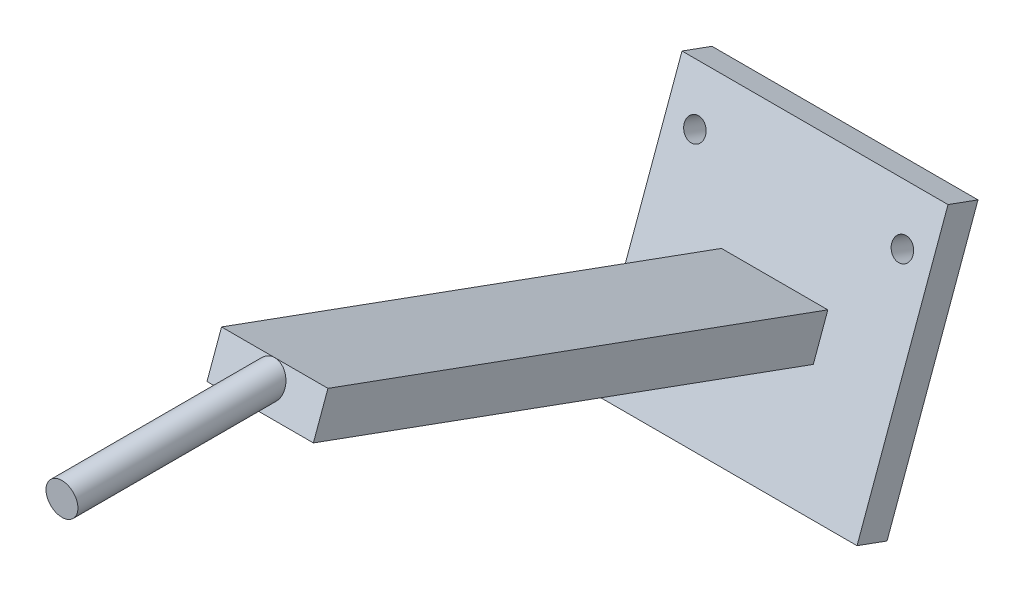
SolidWorks part; units mm, degrees
material "2024 合金"
ref_plane "前视基准面" through (0, 0, 0) normal (0, 0, 1) x (1, 0, 0)
ref_plane "上视基准面" through (0, 0, 0) normal (0, 1, 0) x (1, 0, 0)
ref_plane "右视基准面" through (0, 0, 0) normal (1, 0, 0) x (0, 0, -1)
sketch "草图1" plane through (0, 0, 0) normal (0, 0, 1) x (1, 0, 0)
  circle A0 centre (0, 0) radius 1.5
  dimension "D1" = 3
extrude "凸台-拉伸1" add sketch "草图1" along normal blind 20
sketch "草图2" plane through (0, 0, 0) normal (1, 0, 0) x (0, 0, -1)
  line L0 (0, 1.5) -> (-1.3681, -2.2588)
  line L1 (-1.3681, -2.2588) -> (45.6166, -19.3598)
  line L2 (45.6166, -19.3598) -> (46.9846, -15.601)
  line L3 (46.9846, -15.601) -> (0, 1.5)
  line L4 (0, 0) -> (0, 1.5) construction
  dimension "D1" = 20
  dimension "D2" = 4
  dimension "D3" = 50
extrude "凸台-拉伸2" add sketch "草图2" along normal blind 5 and the other way blind 5
sketch "草图3" plane through (0, -16.9255, -46.5025) normal (0, -0.342, -0.9397) x (-1, 0, 0)
  line L1 (-12.5, 12.5) -> (12.5, 12.5)
  line L2 (-12.5, 12.5) -> (-12.5, -12.5)
  line L3 (-12.5, -12.5) -> (12.5, -12.5)
  line L4 (12.5, 12.5) -> (12.5, -12.5)
  line L5 (-12.5, 12.5) -> (12.5, -12.5) construction
  line L6 (-12.5, -12.5) -> (12.5, 12.5) construction
  point P0 (0, 0)
  dimension "D1" = 25
  dimension "D2" = 25
extrude "凸台-拉伸3" add sketch "草图3" along normal blind 3
sketch "草图4" plane through (0, -17.9516, -49.3216) normal (0, -0.342, -0.9397) x (-1, 0, 0)
  line L0 (-9.75, 8) -> (9.75, 8) construction
  line L1 (0, 0) -> (0, 14.1523) construction
  circle A0 centre (-9.75, 8) radius 1
  circle A1 centre (9.75, 8) radius 1
  point P7 (0, 0)
  dimension "D3" = 2
  dimension "D4" = 2
  dimension "D1" = 16
  dimension "D2" = 19.5
extrude "切除-拉伸1" cut sketch "草图4" against normal through all
